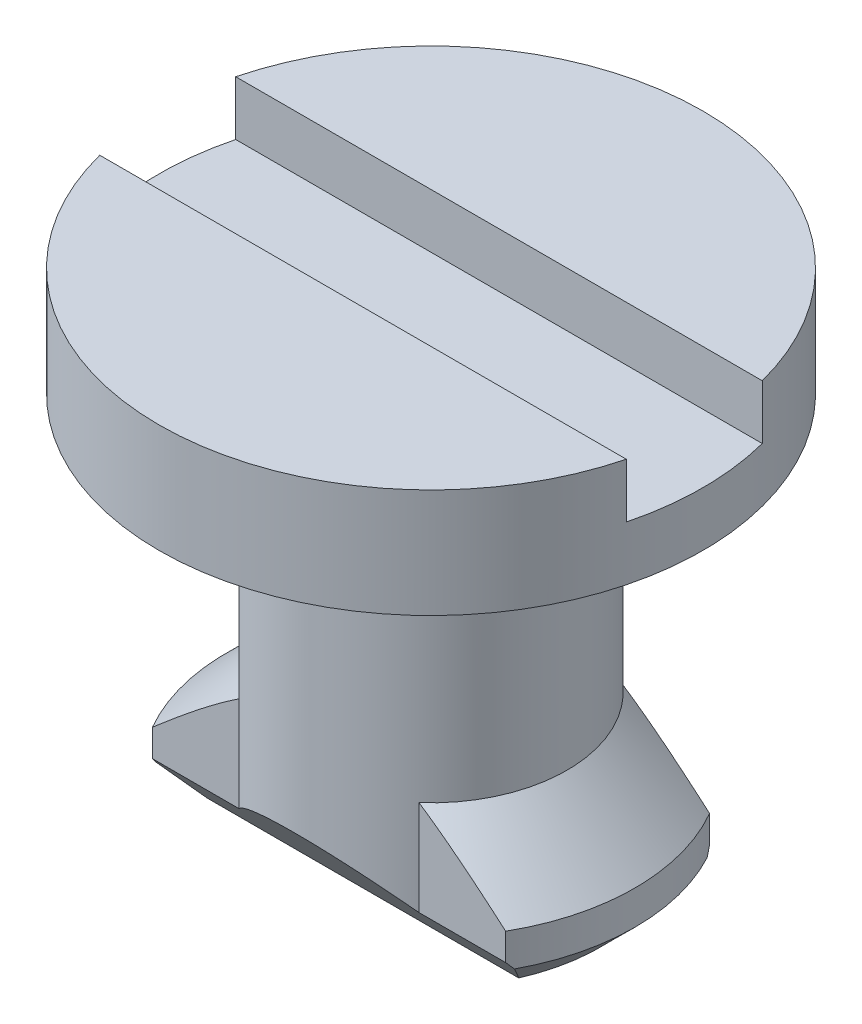
SolidWorks part; units mm, degrees
ref_plane "前视基准面" through (0, 0, 0) normal (0, 0, 1) x (1, 0, 0)
ref_plane "上视基准面" through (0, 0, 0) normal (0, 1, 0) x (1, 0, 0)
ref_plane "右视基准面" through (0, 0, 0) normal (1, 0, 0) x (0, 0, -1)
sketch "草图1" plane through (0, 0, 0) normal (0, 1, 0) x (1, 0, 0)
  circle A0 centre (0, 0) radius 4
  dimension "D1" = 8
extrude "凸台-拉伸1" add sketch "草图1" along normal blind 1
sketch "草图3" plane through (0, 0, 0) normal (0, -1, 0) x (-1, 0, 0)
  circle A0 centre (0, 0) radius 2
  dimension "D1" = 4
extrude "凸台-拉伸3" add sketch "草图3" along normal blind 6.4
sketch "草图4" plane through (0, -6.4, 0) normal (0, -1, 0) x (-1, 0, 0)
  line L1 (2.5981, -1.5) -> (-2.5981, -1.5)
  line L3 (2.5981, 1.5) -> (-2.5981, 1.5)
  arc A0 (2.5981, -1.5) -> (2.5981, 1.5) centre (0, 0) ccw
  arc A1 (-2.5981, 1.5) -> (-2.5981, -1.5) centre (0, 0) ccw
extrude "凸台-拉伸4" add sketch "草图4" against normal blind 2
chamfer "倒角1" distance 0.5 angle 45 2 edges at (3, -6.4, 0) (-3, -6.4, 0)
chamfer "倒角2" distance 1 angle 45 2 edges at (3, -4.4, 0) (-3, -4.4, 0)
sketch "草图5" plane through (0, 0, 0) normal (1, 0, 0) x (0, 0, -1)
  line L0 (0, -6.4154) -> (0, -4.8208) construction
  line L1 (-1.5, -6.4) -> (1.5, -6.4) construction
  line L2 (2, -5.2) -> (1, -6.4)
  line L3 (-2, 0) -> (-2, -6.4) construction
  line L4 (-2, -5.2) -> (-2, -6.4)
  line L5 (-2, -6.4) -> (-1, -6.4)
  line L6 (-2, -5.2) -> (-1, -6.4)
  line L7 (2, -6.4) -> (1, -6.4)
  line L8 (2, -5.2) -> (2, -6.4)
extrude "切除-拉伸1" cut sketch "草图5" against normal up to next and the other way up to next
sketch "草图6" plane through (0, 0, 0) normal (0, -1, 0) x (1, 0, 0)
  circle A0 centre (0, 0) radius 4
  dimension "D1" = 8
extrude "凸台-拉伸5" add sketch "草图6" along normal blind 0.6
sketch "草图7" plane through (0, 1, 0) normal (0, 1, 0) x (1, 0, 0)
  line L0 (4, 1) -> (4, -1)
  line L1 (4, 1) -> (-4, 1)
  line L2 (4, -1) -> (-4, -1)
  line L3 (-4, 1) -> (-4, -1)
  line L4 (4, 1) -> (-4, -1) construction
  line L5 (4, -1) -> (-4, 1) construction
  point P1 (0, 0)
  dimension "D1" = 2
  dimension "D2" = 8
extrude "切除-拉伸2" cut sketch "草图7" against normal blind 0.8
